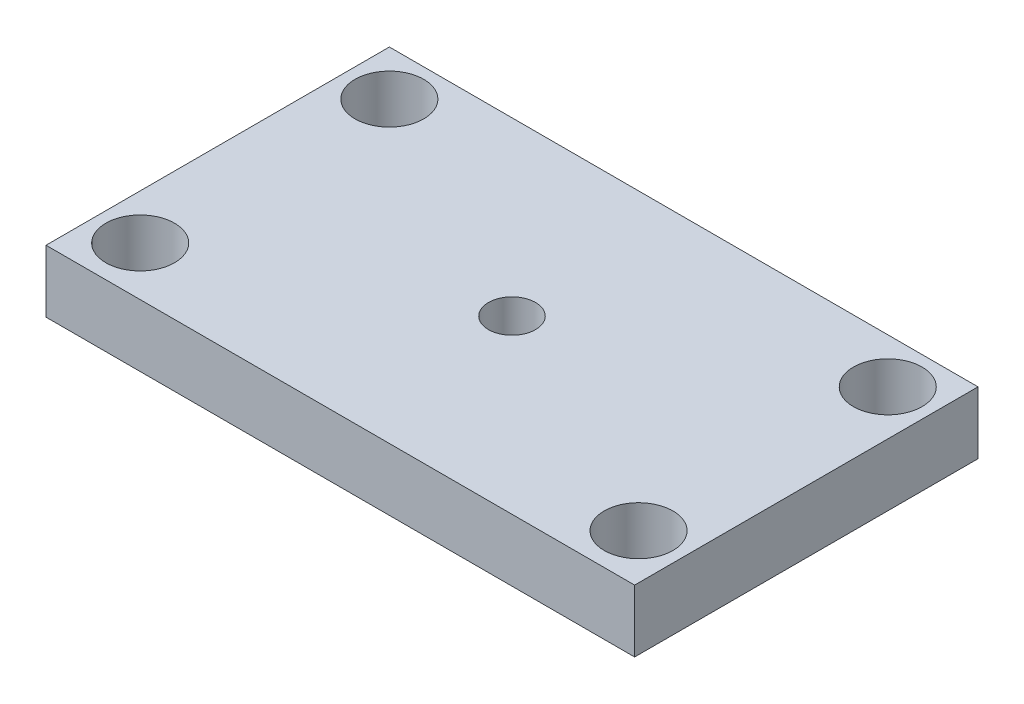
SolidWorks part; units mm, degrees
ref_plane "Front Plane" through (0, 0, 0) normal (0, 0, 1) x (1, 0, 0)
ref_plane "Top Plane" through (0, 0, 0) normal (0, 1, 0) x (1, 0, 0)
ref_plane "Right Plane" through (0, 0, 0) normal (1, 0, 0) x (0, 0, -1)
sketch "Sketch1" plane through (0, 0, 0) normal (0, 1, 0) x (1, 0, 0)
  line L0 (4.6, 30.4) -> (0, 30.4) construction
  line L1 (0, 0) -> (60, 0)
  line L2 (0, 0) -> (0, 35)
  line L3 (0, 35) -> (60, 35)
  line L4 (60, 0) -> (60, 35)
  line L5 (4.6, 30.4) -> (55.4, 30.4) construction
  line L6 (4.6, 30.4) -> (4.6, 5) construction
  line L7 (4.6, 5) -> (55.4, 5) construction
  line L8 (55.4, 30.4) -> (55.4, 5) construction
  line L9 (4.6, 30.4) -> (4.6, 35) construction
  circle A0 centre (4.6, 30.4) radius 3.5
  circle A1 centre (55.4, 30.4) radius 3.5
  circle A2 centre (4.6, 5) radius 3.5
  circle A3 centre (55.4, 5) radius 3.5
  circle A4 centre (30, 17.5) radius 2.4
  point P13 (30, 30.4)
  point P14 (30, 35)
  point P20 (60, 17.5)
  dimension "D5" = 7
  dimension "D6" = 4.8
  dimension "D1" = 60
  dimension "D2" = 35
  dimension "D3" = 50.8
  dimension "D4" = 25.4
extrude "Boss-Extrude1" add sketch "Sketch1" along normal blind 6.35
